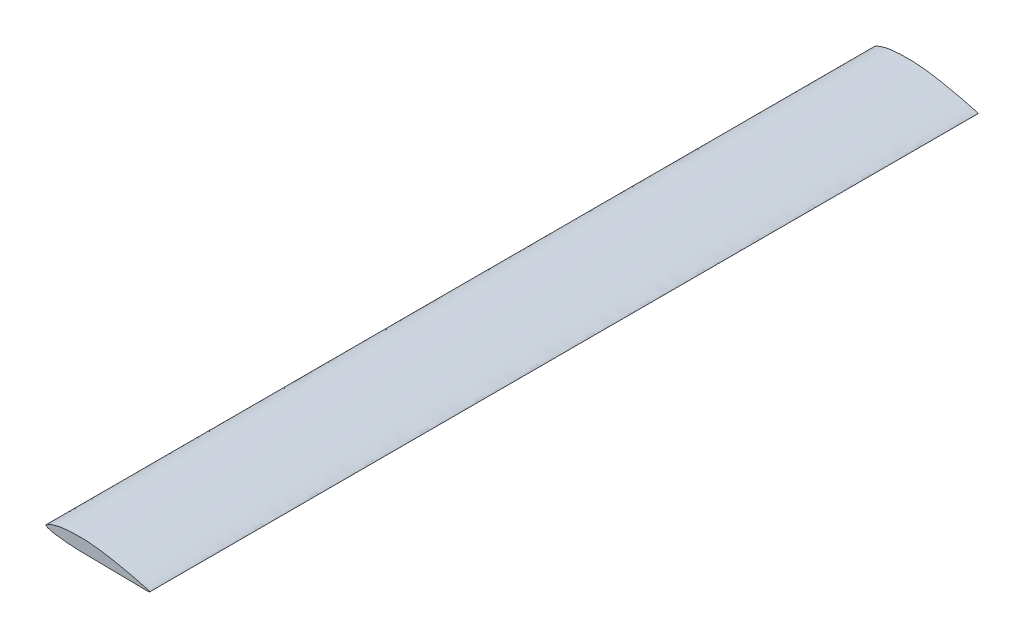
SolidWorks part; units mm, degrees
ref_plane "Front" through (0, 0, 0) normal (0, 0, 1) x (1, 0, 0)
ref_plane "Top" through (0, 0, 0) normal (0, 1, 0) x (1, 0, 0)
ref_plane "Right" through (0, 0, 0) normal (1, 0, 0) x (0, 0, -1)
sketch "Sketch1" plane through (0, 0, 0) normal (0, 0, 1) x (1, 0, 0)
  line L0 (-78.7024, 57.988) -> (132.5152, 57.988) construction
  line L1 (-65.8626, 69.2241) -> (134.1374, 58.2652) construction
  spline S0 degree 3 poles (-52.8425, 63.9957) (-72.7366, 70.1539) (-44.3624, 80.2865) (-26.8739, 82.2444) (1.2158, 83.7507) (28.5532, 81.9579) (56.1203, 77.8213) (85.3282, 71.6332) (105.0956, 67.3941) (144.9663, 57.1606) (98.469, 58.1514) (70.6129, 58.3541) (27.0237, 59.3366) (-6.7164, 59.1799) (-34.9778, 61.6324) (-52.8425, 63.9957) (-72.7366, 70.1539) (-44.3624, 80.2865) knots -0.152493 -0.068172 -0.023231 0 0.043727 0.104026 0.168347 0.238957 0.308437 0.376504 0.446313 0.505134 0.544245 0.677157 0.778294 0.847507 0.931828 0.976769 1 1.043727 1.104026 1.168347 only from (-65.8626, 69.2241) to (-65.8626, 69.2241)
  dimension "D1" = 200
extrude "Boss-Extrude1" add sketch "Sketch1" along normal blind 800 and the other way blind 800
